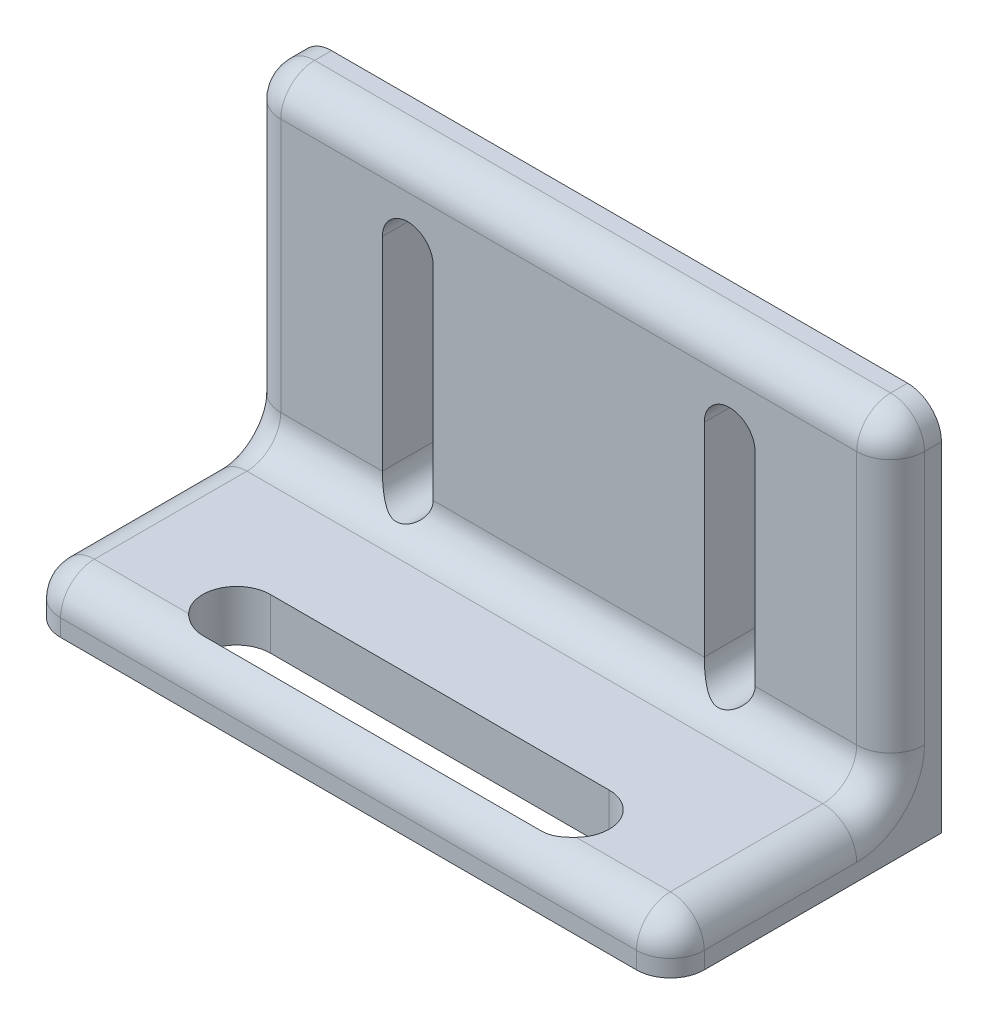
SolidWorks part; units mm, degrees
ref_plane "Front Plane" through (0, 0, 0) normal (0, 0, 1) x (1, 0, 0)
ref_plane "Top Plane" through (0, 0, 0) normal (0, 1, 0) x (1, 0, 0)
ref_plane "Right Plane" through (0, 0, 0) normal (1, 0, 0) x (0, 0, -1)
sketch "Sketch1" plane through (0, 0, 0) normal (0, 0, 1) x (1, 0, 0)
  line L1 (1829.3375, -27) -> (1791.3375, -27)
  line L2 (1829.3375, -27) -> (1829.3375, -5)
  line L3 (1829.3375, -5) -> (1791.3375, -5)
  line L4 (1791.3375, -27) -> (1791.3375, -5)
  dimension "D1" = 22
extrude "Boss-Extrude1" add sketch "Sketch1" along normal blind 3
sketch "Sketch2" plane through (0, 0, 0) normal (0, 0, -1) x (-1, 0, 0)
  line L0 (-1791.3375, -16) -> (-1829.3375, -16) construction
  line L1 (-1791.3375, -5) -> (-1791.3375, -27) construction
  line L2 (-1829.3375, -27) -> (-1829.3375, -5) construction
  line L3 (-1810.3375, -16) -> (-1791.3375, -16) construction
  line L4 (-1810.3375, -16) -> (-1810.3375, -29)
  line L5 (-1793.3375, -29) -> (-1827.3375, -29) construction
  line L6 (-1819.8375, -10) -> (-1819.8375, -22) construction
  line L7 (-1818.3375, -10) -> (-1818.3375, -22)
  line L8 (-1821.3375, -10) -> (-1821.3375, -22)
  line L9 (-1800.8375, -10) -> (-1800.8375, -22) construction
  line L10 (-1802.3375, -10) -> (-1802.3375, -22)
  line L11 (-1799.3375, -10) -> (-1799.3375, -22)
  circle A0 centre (-1800.8375, -16) radius 1.5 construction
  circle A1 centre (-1819.8375, -16) radius 1.5 construction
  arc A2 (-1818.3375, -10) -> (-1821.3375, -10) centre (-1819.8375, -10) ccw
  arc A3 (-1821.3375, -22) -> (-1818.3375, -22) centre (-1819.8375, -22) ccw
  arc A4 (-1802.3375, -10) -> (-1799.3375, -10) centre (-1800.8375, -10) cw
  arc A5 (-1799.3375, -22) -> (-1802.3375, -22) centre (-1800.8375, -22) cw
  point P16 (-1819.8375, -16)
  point P21 (-1819.8375, -23.5)
  point P24 (-1800.8375, -16)
  dimension "D1" = 3
  dimension "D2" = 12
  dimension "D3" = 1.5
extrude "Cut-Extrude1" cut sketch "Sketch2" against normal blind 3 contours L3 A0 | L3 A0 | A1 L0 | A1 L0 | A5 L11 A4 L10 | L8 A3 L7 A2 region at (1819.8375, -16, 0) region at (1800.8375, -16, 0)
sketch "Sketch3" plane through (0, 0, 3) normal (0, 0, 1) x (1, 0, 0)
  line L0 (1829.3375, -27) -> (1829.3375, -5) construction
  line L1 (1791.3375, -27) -> (1829.3375, -27)
  line L2 (1791.3375, -27) -> (1791.3375, -24)
  line L3 (1791.3375, -24) -> (1829.3375, -24)
  line L4 (1829.3375, -27) -> (1829.3375, -24)
  dimension "D1" = 3
extrude "Boss-Extrude2" add sketch "Sketch3" along normal blind 13
sketch "Sketch4" plane through (0, -27.7162, 0) normal (0, -1, 0) x (1, 0, 0)
  line L0 (1815.3255, 12.61) -> (1805.8255, 12.61) construction
  line L1 (1810.3375, 0) -> (1810.3375, 16)
  line L2 (1820.3375, 12.61) -> (1800.3375, 12.61) construction
  line L3 (1820.3375, 10.61) -> (1800.3375, 10.61)
  line L4 (1820.3375, 14.61) -> (1800.3375, 14.61)
  line L5 (1791.3375, 0) -> (1829.3375, 0)
  line L6 (1829.3375, 0) -> (1829.3375, 16)
  line L7 (1829.3375, 16) -> (1791.3375, 16)
  line L8 (1791.3375, 16) -> (1791.3375, 0)
  line L9 (1791.3375, 0) -> (1829.3375, 0)
  line L10 (1819.5755, 16.86) -> (1801.5755, 16.86)
  line L11 (1801.5755, 16.86) -> (1801.5755, 9.86)
  line L12 (1801.5755, 9.86) -> (1804.3255, 9.86)
  line L13 (1804.3255, 9.86) -> (1804.3255, 10.9329)
  line L14 (1807.3255, 10.9329) -> (1807.3255, 9.86)
  line L15 (1807.3255, 9.86) -> (1813.8255, 9.86)
  line L16 (1813.8255, 9.86) -> (1813.8255, 10.9329)
  line L17 (1816.8255, 10.9329) -> (1816.8255, 9.86)
  line L18 (1816.8255, 9.86) -> (1819.5755, 9.86)
  line L19 (1819.5755, 9.86) -> (1819.5755, 16.86)
  line L20 (1819.5755, 16.86) -> (1801.5755, 16.86)
  line L21 (1801.5755, 16.86) -> (1801.5755, 9.86) construction
  line L22 (1801.5755, 9.86) -> (1804.3255, 9.86)
  line L23 (1804.3255, 9.86) -> (1804.3255, 10.9329)
  line L24 (1807.3255, 10.9329) -> (1807.3255, 9.86)
  line L25 (1807.3255, 9.86) -> (1813.8255, 9.86)
  line L26 (1813.8255, 9.86) -> (1813.8255, 10.9329)
  line L27 (1816.8255, 10.9329) -> (1816.8255, 9.86)
  line L28 (1816.8255, 9.86) -> (1819.5755, 9.86)
  line L29 (1819.5755, 9.86) -> (1819.5755, 16.86) construction
  line L30 (1829.3375, 0) -> (1829.3375, 16)
  line L31 (1829.3375, 16) -> (1791.3375, 16)
  line L32 (1791.3375, 16) -> (1791.3375, 0)
  arc A0 (1820.3375, 10.61) -> (1820.3375, 14.61) centre (1820.3375, 12.61) ccw
  arc A1 (1800.3375, 14.61) -> (1800.3375, 10.61) centre (1800.3375, 12.61) ccw
  arc A2 (1807.3255, 10.9329) -> (1804.3255, 10.9329) centre (1805.8255, 12.61) ccw
  arc A3 (1816.8255, 10.9329) -> (1813.8255, 10.9329) centre (1815.3255, 12.61) ccw
  arc A4 (1807.3255, 10.9329) -> (1804.3255, 10.9329) centre (1805.8255, 12.61) ccw construction
  arc A5 (1816.8255, 10.9329) -> (1813.8255, 10.9329) centre (1815.3255, 12.61) ccw construction
  point P24 (1810.3375, 12.61)
  line M15 (1801.5755, 16.86) -> (1801.5755, 9.86)
  line M17 (1804.3255, 9.86) -> (1804.3255, 10.9329)
  arc M18 (1804.3255, 10.9329) -> (1807.3255, 10.9329) centre (1805.8255, 12.61) cw
  line M19 (1807.3255, 10.9329) -> (1807.3255, 9.86)
  line M21 (1813.8255, 9.86) -> (1813.8255, 10.9329)
  arc M22 (1813.8255, 10.9329) -> (1816.8255, 10.9329) centre (1815.3255, 12.61) cw
  line M23 (1816.8255, 10.9329) -> (1816.8255, 9.86)
  line M25 (1819.5755, 9.86) -> (1819.5755, 16.86)
  dimension "D2" = 0
  dimension "D3" = 4
  dimension "D4" = 20
  dimension "D1" = 0
extrude "Cut-Extrude2" cut sketch "Sketch4" against normal blind 13 contours L4 A1 L3 M15 | L4 L3 M18 M15 M17 | L4 L3 M18 M17 M19 | L1 L4 L3 M18 M19 | L4 L1 L3 M22 M21 | L4 L3 M22 M21 M23 | L4 L3 M25 M22 M23 | L3 A0 L4 M25 region at (1809.0223, -27.7162, 12.6226) region at (1811.8879, -27.7162, 12.6206) region at (1815.3255, -27.7162, 12.593) region at (1805.8255, -27.7162, 12.593) region at (1818.3892, -27.7162, 12.624) region at (1802.7618, -27.7162, 12.624) region at (1800.1356, -27.7162, 12.61) region at (1820.7846, -27.7162, 12.61)
fillet "Fillet1" radius 2 11 edges at (1829.3375, -24, 9.5) (1791.3375, -24, 9.5) (1829.3375, -14.5, 3) (1791.3375, -14.5, 3) (1810.3375, -5, 3) (1791.3375, -5, 1.5) (1829.3375, -5, 1.5) (1791.3375, -25.5, 16) (1829.3375, -25.5, 16) (1810.3375, -24, 3) (1810.3375, -24, 16)
equation "\"12mmmm\"=9.5"
